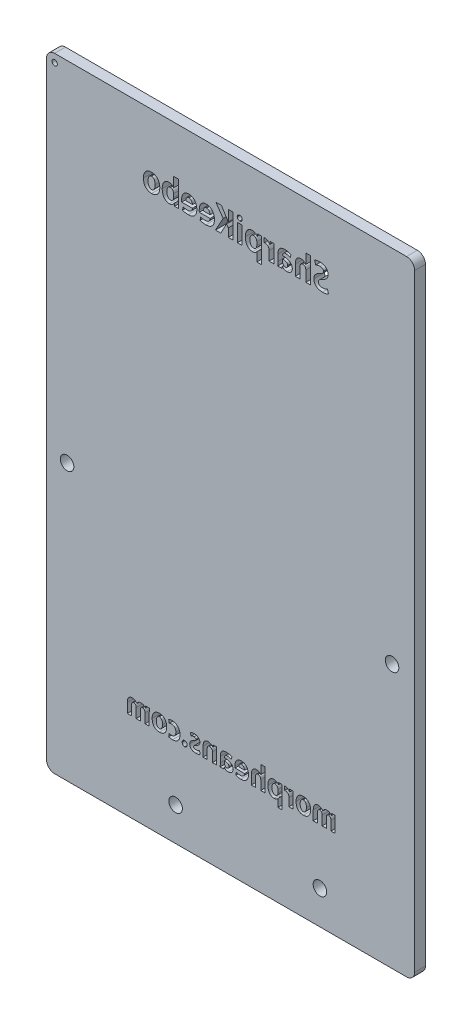
SolidWorks part; units mm, degrees
material "Plastique personnalisé"
ref_plane "Plan de face" through (0, 0, 0) normal (0, 0, 1) x (1, 0, 0)
ref_plane "Plan de dessus" through (0, 0, 0) normal (0, 1, 0) x (1, 0, 0)
ref_plane "Plan de droite" through (0, 0, 0) normal (1, 0, 0) x (0, 0, -1)
sketch "Esquisse1" plane through (0, 0, 0) normal (0, 0, 1) x (1, 0, 0)
  line L0 (150.4918, -120.1916) -> (148.59, -120.1916) construction
  line L1 (149.84, -48.26) -> (213.38, -48.26)
  line L3 (149.59, -163.576) -> (213.63, -163.576)
  line L5 (213.329, -157.77) -> (214.63, -157.77) construction
  line L7 (211.729, -159.87) -> (211.729, -163.576) construction
  line L9 (211.729, -161.723) -> (213.9795, -161.723) construction
  line L10 (152.166, -118.078) -> (152.166, -115.9321) construction
  line L12 (171.45, -157.48) -> (174.45, -157.48) construction
  line L28 (168.45, -160.226) -> (174.45, -154.734) construction
  line L29 (168.45, -154.734) -> (174.45, -160.226) construction
  line L39 (148.632, -115.1937) -> (154.136, -110.3583) construction
  line L40 (148.632, -110.3583) -> (154.136, -115.1937) construction
  line L46 (215.8814, -117.435) -> (208.8197, -113.4466) construction
  line L47 (215.8814, -112.435) -> (207.0286, -117.435) construction
  line L48 (148.59, -49.51) -> (147.5926, -49.51) construction
  line L53 (147.5926, -49.51) -> (147.5926, -48.3587) construction
  line L54 (214.63, -162.576) -> (215.6269, -162.576) construction
  line L55 (215.6269, -162.576) -> (215.6269, -163.6747) construction
  line L56 (198.12, -157.48) -> (201.1151, -157.48) construction
  line L57 (214.1269, -163.6747) -> (149.0926, -163.6747)
  line L58 (215.6269, -162.1747) -> (215.6269, -49.8587)
  line L59 (214.1269, -48.3587) -> (149.0926, -48.3587)
  line L60 (147.5926, -162.1747) -> (147.5926, -49.8587)
  line L66 (195.1249, -160.226) -> (201.1151, -154.734) construction
  line L67 (195.1249, -154.734) -> (201.1151, -160.226) construction
  circle A4 centre (151.384, -112.776) radius 1.25
  circle A5 centre (211.455, -114.935) radius 1.25
  circle A6 centre (198.12, -157.48) radius 1.25
  circle A7 centre (171.45, -157.48) radius 1.25
  arc A14 (215.6269, -162.1747) -> (214.1269, -163.6747) centre (214.1269, -162.1747) cw
  arc A15 (215.6269, -49.8587) -> (214.1269, -48.3587) centre (214.1269, -49.8587) ccw
  arc A16 (147.5926, -49.8587) -> (149.0926, -48.3587) centre (149.0926, -49.8587) cw
  arc A17 (149.0926, -163.6747) -> (147.5926, -162.1747) centre (149.0926, -162.1747) cw
  point P127 (174.45, -161.723)
  point P130 (201.1151, -161.723)
  dimension "D1" = 1.5
  dimension "D3" = 3
  dimension "D6" = 5
extrude "Boss.-Extru.1" add sketch "Esquisse1" along normal blind 2 contours A17 L57 A14 L58 A15 L59 A16 L60 A7 A6 A5 A4 region at (181.606, -105.9423, 0)
sketch "Esquisse2" plane through (0, 0, 2) normal (0, 0, 1) x (1, 0, 0)
  circle A0 centre (149.0926, -49.8587) radius 0.5
extrude "Enlèv. mat.-Extru.1" cut sketch "Esquisse2" against normal blind 2
sketch "Esquisse3" plane through (0, 0, 0) normal (0, 0, -1) x (-1, 0, 0)
  text T0 "SharpiKeebo" font "@Adobe Gothic Std B" height 4.5
extrude "Enlèv. mat.-Extru.2" cut sketch "Esquisse3" against normal blind 2
sketch "Esquisse4" plane through (0, 0, 0) normal (0, 0, -1) x (-1, 0, 0)
  text T0 "morpheans.com" font "@Adobe Gothic Std B" height 4
extrude "Enlèv. mat.-Extru.3" cut sketch "Esquisse4" against normal blind 2
